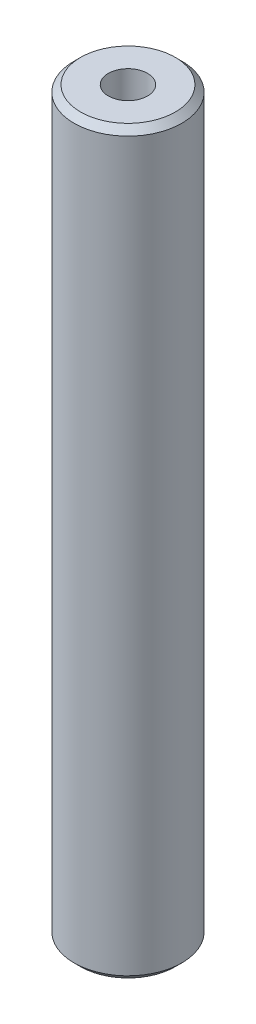
SolidWorks part; units mm, degrees
ref_plane "Front Plane" through (0, 0, 0) normal (0, 0, 1) x (1, 0, 0)
ref_plane "Top Plane" through (0, 0, 0) normal (0, 1, 0) x (1, 0, 0)
ref_plane "Right Plane" through (0, 0, 0) normal (1, 0, 0) x (0, 0, -1)
sketch "Sketch1" plane through (0, 0, 0) normal (0, 1, 0) x (1, 0, 0)
  circle A0 centre (0, 0) radius 35
  dimension "SHAFT_OD" = 70
extrude "Boss-Extrude1" add sketch "Sketch1" along normal blind 480.8469
sketch "Sketch2" plane through (0, 0, 0) normal (0, 1, 0) x (1, 0, 0)
  circle A0 centre (0, 0) radius 12.7483
  dimension "BORE_D" = 25.4966
extrude "Cut-Extrude1" cut sketch "Sketch2" along normal through all
chamfer "Chamfer1" distance 4.2232 angle 45 2 edges at (0, 480.8469, 35) (0, 0, 35)
